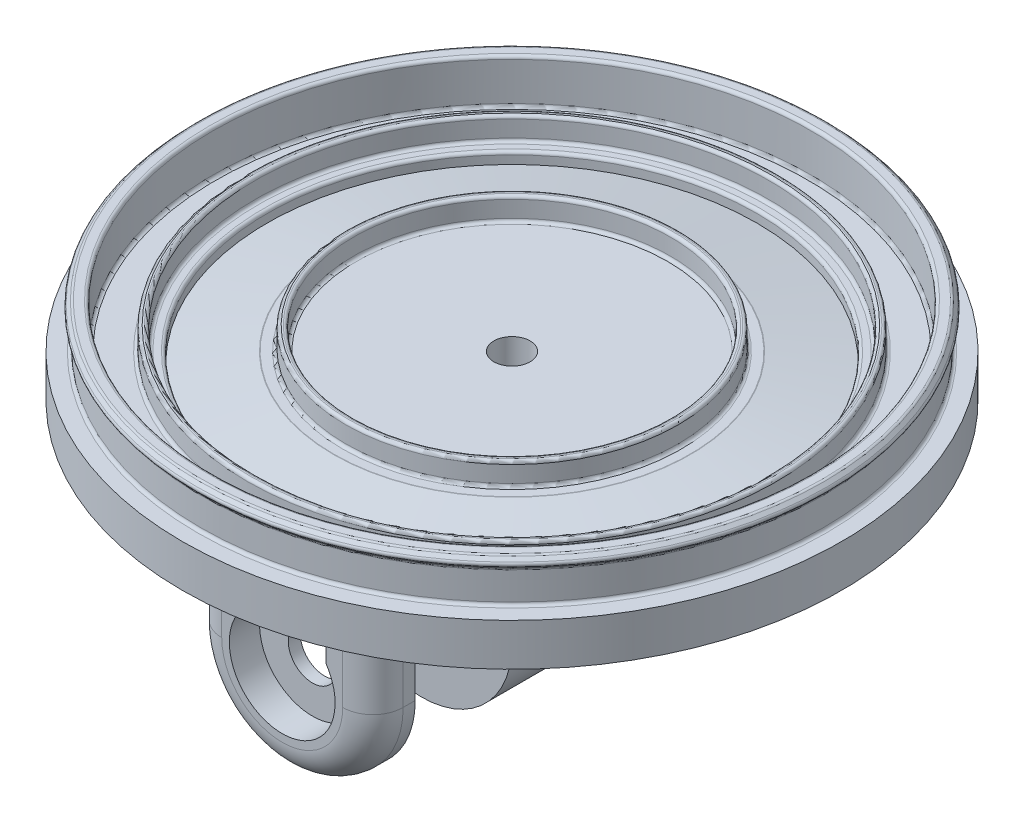
SolidWorks part; units mm, degrees
material "PLA"
ref_plane "Front Plane" through (0, 0, 0) normal (0, 0, 1) x (1, 0, 0)
ref_plane "Top Plane" through (0, 0, 0) normal (0, 1, 0) x (1, 0, 0)
ref_plane "Right Plane" through (0, 0, 0) normal (1, 0, 0) x (0, 0, -1)
sketch "Sketch2" plane through (0, 0, 0) normal (0, 1, 0) x (1, 0, 0)
  circle A0 centre (0, 0) radius 54.5
  dimension "D1" = 109
extrude "Boss-Extrude1" add sketch "Sketch2" along normal blind 7
sketch "Sketch3" plane through (0, 0, 0) normal (0, 0, 1) x (1, 0, 0)
  line L0 (0, 0) -> (0, 7) construction
  line L1 (54.5, 7) -> (-54.5, 7) construction
  line L2 (0, 7) -> (-29.5, 7) construction
  line L3 (-29.5, 7) -> (-40.5, 7)
  line L4 (-40.5, 7) -> (-40.5, 5.127)
  line L5 (-40.5, 5.127) -> (-29.5, 7)
  dimension "D1" = 29.5
  dimension "D2" = 11
  dimension "D3" = 1.873
revolve "Cut-Revolve1" cut sketch "Sketch3" angle 360 about L0
sketch "Sketch4" plane through (0, 7, 0) normal (0, 1, 0) x (1, 0, 0)
  circle A0 centre (0, 0) radius 43.75
  circle A1 centre (0, 0) radius 42.5
  circle A2 centre (0, 0) radius 27.5
  circle A3 centre (0, 0) radius 26.25
  dimension "D1" = 87.5
  dimension "D2" = 85
  dimension "D3" = 55
  dimension "D4" = 52.5
extrude "Boss-Extrude2" add sketch "Sketch4" along normal blind 3.723 contours A0 A1 | A2 A3 region at (-42.5126, 7, 0) region at (-26.7222, 7, 0)
fillet "Fillet1" radius 0.5 10 edges at (0, 7, 26.25) (0, 7, -29.5) (0, 7, -40.5) (0, 10.723, 43.75) (0, 7, 42.5) (0, 10.723, 42.5) (0, 7, 27.5) (0, 10.723, 27.5) (0, 10.723, 26.25) (0, 7, 43.75)
sketch "Sketch5" plane through (0, 0, 0) normal (0, 0, 1) x (1, 0, 0)
  line L0 (0, 7) -> (-49.5, 7) construction
  line L1 (54.5, 7) -> (-54.5, 7) construction
  line L2 (0, 7) -> (0, 24.3916) construction
  line L3 (0, -55) -> (0, 55) construction
  line L4 (-49.5, 7) -> (-51.5, 7)
  line L5 (-51.5, 7) -> (-51.5, 12.323)
  line L6 (-51.5, 12.323) -> (-52.5, 13.323)
  line L7 (-52.5, 13.323) -> (-51.5, 14.323)
  line L8 (-51.5, 14.323) -> (-49.5, 14.323)
  line L9 (-49.5, 14.323) -> (-49.5, 7)
  dimension "D1" = 7.323
  dimension "D2" = 1
  dimension "D3" = 1
  dimension "D4" = 2
  dimension "D5" = 2
  dimension "D6" = 49.5
revolve "Revolve1" add sketch "Sketch5" angle 360 about L2
fillet "Fillet2" radius 0.5 6 edges at (51.5, 7, 0) (49.5, 7, 0) (49.5, 14.323, 0) (51.5, 14.323, 0) (51.5, 12.323, 0) (52.5, 13.323, 0)
sketch "Sketch6" plane through (0, 7, 0) normal (0, 1, 0) x (1, 0, 0)
  circle A0 centre (0, 0) radius 3
  dimension "D1" = 6
extrude "Cut-Extrude1" cut sketch "Sketch6" against normal blind 6
sketch "Sketch7" plane through (0, 0, 0) normal (0, 0, 1) x (1, 0, 0)
  line L0 (-54.5, 0) -> (54.5, 0) construction
  line L1 (-15, 0) -> (15, 0)
  line L2 (-15, 0) -> (-15, -20)
  line L3 (-15, -20) -> (15, -20)
  line L4 (15, 0) -> (15, -20)
  line L5 (-15, -20) -> (-11.025, -20)
  line L6 (11.025, -20) -> (15, -20)
  circle A0 centre (0, -20) radius 15
  circle A1 centre (0, -20) radius 11.025
  arc A2 (11.025, -20) -> (-11.025, -20) centre (0, -20) ccw
  circle A3 centre (0, -20) radius 4
  point P8 (0, 0)
  dimension "D1" = 30
  dimension "D3" = 22.05
  dimension "D4" = 8
  dimension "D2" = 20
extrude "Boss-Extrude3" add sketch "Sketch7" along normal blind 15 and the other way blind 15 contours A0 L4 L1 L2 | A1 L3 A0 | A1 L3 A0 | L3 A1 | L3 A1 region at (0, -4.7914, 0) region at (0, -5.3354, 0) region at (-13.0125, -20.3354, 0) region at (0, -14.8689, 0) region at (0, -25.1311, 0)
sketch "Sketch10" plane through (0, 0, 0) normal (0, 0, 1) x (1, 0, 0)
  line L0 (-54.5, 0) -> (54.5, 0) construction
  line L1 (20.9531, 0) -> (-17.5201, 0)
  line L2 (20.9531, 0) -> (20.9531, -42.1824)
  line L3 (20.9531, -42.1824) -> (-17.5201, -42.1824)
  line L4 (-17.5201, 0) -> (-17.5201, -42.1824)
extrude "Cut-Extrude4" cut sketch "Sketch10" against normal blind 5 and the other way blind 5
sketch "Sketch11" plane through (0, 0, 15) normal (0, 0, 1) x (1, 0, 0)
  line L0 (15, 0) -> (15, -20)
  line L1 (59.95, 0) -> (-59.95, 0) construction
  line L2 (15, 0) -> (15, -20) construction
  line L3 (-15, -20) -> (-15, 0)
  line L4 (-15, 0) -> (-15, -20) construction
  line L5 (-15, 0) -> (15, 0)
  arc A0 (15, -20) -> (-15, -20) centre (0, -20) cw
  circle A1 centre (0, -20) radius 3.5
  circle M5 centre (0, -20) radius 4
  arc M6 (-15, -20) -> (15, -20) centre (0, -20) ccw
  line M7 (15, -20) -> (15, 0)
  line M8 (15, 0) -> (-15, 0)
  line M9 (-15, 0) -> (-15, -20)
  dimension "D1" = 7
extrude "Boss-Extrude4" add sketch "Sketch11" along normal blind 2 from offset 16 contours M9 M6 M7 M8 M5 region at (0, -15.8479, 15)
sketch "Sketch12" plane through (0, 0, 33) normal (0, 0, 1) x (1, 0, 0)
  line L0 (-7.25, 0) -> (-7.25, -15.101)
  line L1 (59.95, 0) -> (-59.95, 0) construction
  line L2 (7.25, 0) -> (7.25, -15.101)
  line L3 (0, -27.1277) -> (0, 27.1277) construction
  line L4 (-7.25, 0) -> (7.25, 0)
  line L5 (-7.25, 0) -> (-15, 0)
  line L6 (-15, 0) -> (-15, -20) construction
  line L7 (7.25, 0) -> (15, 0)
  line L8 (15, -20) -> (15, 0) construction
  line L9 (15, 0) -> (15, -20)
  circle A0 centre (0, -20) radius 8.75
  arc A1 (15, -20) -> (-15, -20) centre (0, -20) cw
  arc A2 (-15, -20) -> (15, -20) centre (0, -20) ccw construction
  line M4 (-15, 0) -> (-15, -20)
  arc M5 (-15, -20) -> (15, -20) centre (0, -20) ccw
  line M6 (15, -20) -> (15, 0)
  line M7 (15, 0) -> (-15, 0)
  dimension "D1" = 17.5
  dimension "D2" = 14.5
  dimension "D3" = 7.25
extrude "Boss-Extrude5" add sketch "Sketch12" along normal blind 5 contours A0 L0 L2 M7 M4 M5 M6 region at (-7.711, -7.5505, 33)
fillet "Fillet3" radius 5 3 edges at (11.125, 0, 38) (-11.125, 0, 38) (-15, -10, 38)
